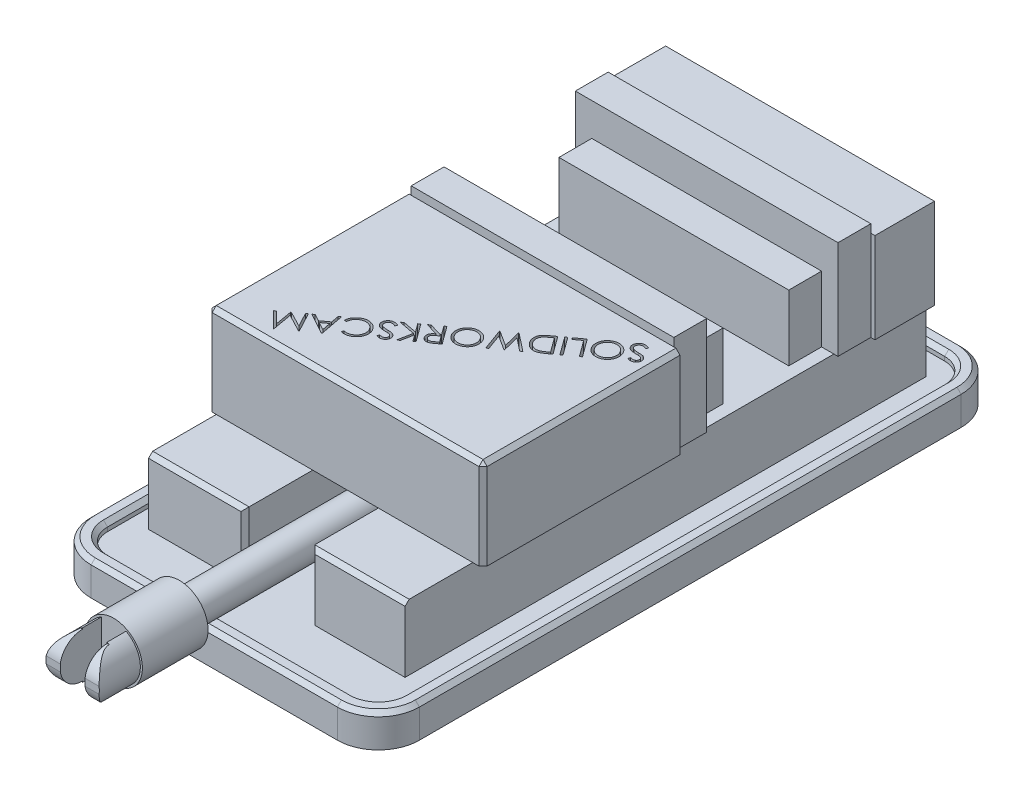
SolidWorks part; units mm, degrees
ref_plane "Plane1" through (0, 0, 0) normal (0, 0, 1) x (1, 0, 0)
ref_plane "Plane2" through (0, 0, 0) normal (0, 1, 0) x (1, 0, 0)
ref_plane "Plane3" through (0, 0, 0) normal (1, 0, 0) x (0, 0, -1)
sketch "Sketch1" plane through (0, 0, 0) normal (0, 0, 1) x (1, 0, 0)
  line L1 (-101.6, 0) -> (101.6, 0)
  line L2 (-101.6, 0) -> (-101.6, 76.2)
  line L3 (-101.6, 76.2) -> (101.6, 76.2)
  line L4 (101.6, 0) -> (101.6, 76.2)
extrude "Base-Extrude" add sketch "Sketch1" against normal blind 25.4
sketch "Sketch2" plane through (0, 0, 0) normal (0, 0, 1) x (1, 0, 0)
  line L0 (-101.6, 0) -> (101.6, 0) construction
  line L1 (-106.3625, 0) -> (106.3625, 0)
  line L2 (-106.3625, 0) -> (-106.3625, 69.85)
  line L3 (-106.3625, 69.85) -> (106.3625, 69.85)
  line L4 (106.3625, 0) -> (106.3625, 69.85)
  dimension "D1" = 69.85
extrude "Boss-Extrude1" add sketch "Sketch2" along normal blind 152.4
sketch "Sketch3" plane through (0, 0, 0) normal (0, -1, 0) x (1, 0, 0)
  line L1 (98.425, 204.7875) -> (25.4, 204.7875)
  line L2 (98.425, 204.7875) -> (98.425, -201.6125)
  line L3 (98.425, -201.6125) -> (25.4, -201.6125)
  line L4 (25.4, 204.7875) -> (25.4, -201.6125)
  line L5 (-100.0125, 204.7875) -> (-25.4, 204.7875)
  line L6 (-100.0125, 204.7875) -> (-100.0125, -201.6125)
  line L7 (-100.0125, -201.6125) -> (-25.4, -201.6125)
  line L8 (-25.4, 204.7875) -> (-25.4, -201.6125)
extrude "Boss-Extrude2" add sketch "Sketch3" along normal blind 50.8
sketch "Sketch4" plane through (0, 0, 0) normal (0, 1, 0) x (-1, 0, 0)
  line L1 (-104.775, -201.6125) -> (106.3625, -201.6125)
  line L2 (-104.775, -201.6125) -> (-104.775, -152.4)
  line L3 (-104.775, -152.4) -> (106.3625, -152.4)
  line L4 (106.3625, -201.6125) -> (106.3625, -152.4)
extrude "Boss-Extrude3" add sketch "Sketch4" along normal blind 69.85
sketch "Sketch5" plane through (0, 0, -152.4) normal (0, 0, 1) x (1, 0, 0)
  line L1 (-101.6, 0) -> (101.6, 0)
  line L2 (-101.6, 0) -> (-101.6, 76.2)
  line L3 (-101.6, 76.2) -> (101.6, 76.2)
  line L4 (101.6, 0) -> (101.6, 76.2)
extrude "Boss-Extrude4" add sketch "Sketch5" along normal blind 25.4
sketch "Sketch6" plane through (0, -50.8, 0) normal (0, -1, 0) x (1, 0, 0)
  line L1 (-95.25, 254) -> (95.25, 254)
  line L2 (-127, 222.25) -> (-127, -196.85)
  line L3 (-95.25, -228.6) -> (95.25, -228.6)
  line L4 (127, 222.25) -> (127, -196.85)
  arc A0 (127, 222.25) -> (95.25, 254) centre (95.25, 222.25) ccw
  arc A1 (-127, 222.25) -> (-95.25, 254) centre (-95.25, 222.25) cw
  arc A2 (-95.25, -228.6) -> (-127, -196.85) centre (-95.25, -196.85) cw
  arc A3 (127, -196.85) -> (95.25, -228.6) centre (95.25, -196.85) cw
  dimension "D1" = 31.75
extrude "Boss-Extrude5" add sketch "Sketch6" along normal blind 19.05
sketch "Sketch7" plane through (0, -69.85, 0) normal (0, -1, 0) x (1, 0, 0)
  line L1 (95.25, 254) -> (-95.25, 254)
  line L2 (127, 222.25) -> (127, -196.85)
  line L3 (95.25, -228.6) -> (-95.25, -228.6)
  line L4 (-127, 222.25) -> (-127, -196.85)
  line L5 (95.25, 241.3) -> (-95.25, 241.3)
  line L6 (114.3, 222.25) -> (114.3, -196.85)
  line L7 (95.25, -215.9) -> (-95.25, -215.9)
  line L8 (-114.3, 222.25) -> (-114.3, -196.85)
  arc A0 (-114.3, -196.85) -> (-95.25, -215.9) centre (-95.25, -196.85) ccw
  arc A1 (95.25, -215.9) -> (114.3, -196.85) centre (95.25, -196.85) ccw
  arc A2 (114.3, 222.25) -> (95.25, 241.3) centre (95.25, 222.25) ccw
  arc A3 (-114.3, 222.25) -> (-95.25, 241.3) centre (-95.25, 222.25) cw
  arc A4 (-127, 222.25) -> (-95.25, 254) centre (-95.25, 222.25) cw
  arc A5 (127, 222.25) -> (95.25, 254) centre (95.25, 222.25) ccw
  arc A6 (95.25, -228.6) -> (127, -196.85) centre (95.25, -196.85) ccw
  arc A7 (-127, -196.85) -> (-95.25, -228.6) centre (-95.25, -196.85) ccw
  point P22 (127, 254)
  point P27 (-127, -228.6)
extrude "Boss-Extrude6" add sketch "Sketch7" against normal blind 25.4
sketch "Sketch8" plane through (0, 0, -201.6125) normal (0, 0, -1) x (-1, 0, 0)
  line L0 (-25.4, 0) -> (25.4, 0) construction
  line L1 (-19.05, 0) -> (19.05, 0)
  line L2 (-19.05, 0) -> (-19.05, -19.0525)
  line L3 (-0.0025, -38.1) -> (0.0025, -38.1)
  line L4 (19.05, 0) -> (19.05, -19.0525)
  arc A0 (-0.0025, -38.1) -> (-19.05, -19.0525) centre (-0.0025, -19.0525) cw
  arc A1 (19.05, -19.0525) -> (0.0025, -38.1) centre (0.0025, -19.0525) cw
  dimension "D1" = 19.0475
extrude "Boss-Extrude7" add sketch "Sketch8" against normal blind 50.8
sketch "Sketch9" plane through (0, 0, -150.8125) normal (0, 0, 1) x (1, 0, 0)
  circle A0 centre (-0.0025, -19.0525) radius 12.6992
extrude "Boss-Extrude8" add sketch "Sketch9" along normal blind 482.6
sketch "Sketch10" plane through (0, 0, 331.7875) normal (0, 0, 1) x (1, 0, 0)
  circle A0 centre (-0.0025, -19.0525) radius 22.225
  dimension "D1" = 44.45
extrude "Boss-Extrude9" add sketch "Sketch10" against normal blind 50.8
sketch "Sketch12" plane through (0, 0, 331.7875) normal (0, 0, 1) x (1, 0, 0)
  line L0 (-9.5647, -0.7628) -> (-9.5647, -37.3372)
  line L1 (9.5596, -0.7601) -> (9.5596, -37.3399)
  arc A2 (-9.5647, -0.7628) -> (-9.5647, -37.3372) centre (0, -19.05) ccw
  arc A3 (9.5596, -37.3399) -> (9.5596, -0.7601) centre (0, -19.05) ccw
extrude "Boss-Extrude10" add sketch "Sketch12" along normal blind 31.75
sketch "Sketch13" plane through (0, 0, 0) normal (1, 0, 0) x (0, 0, -1)
  line L0 (-280.9875, -19.0525) -> (150.8125, -19.0525) construction
  line L1 (-346.3741, 4.5289) -> (-346.3741, -1.682)
  line L2 (-346.3741, -36.4231) -> (-346.3741, -44.7128)
  line L3 (-346.3741, 4.5289) -> (-380.0007, 4.5289)
  line L4 (-380.0007, 4.5289) -> (-380.0007, -44.7128)
  line L5 (-380.0007, -44.7128) -> (-346.3741, -44.7128)
  arc A0 (-346.3741, -1.682) -> (-346.3741, -36.4231) centre (-346.3741, -19.0525) ccw
extrude "Cut-Extrude3" cut sketch "Sketch13" against normal through all and the other way blind 31.75
sketch "Sketch14" plane through (9.5596, 0, 0) normal (-1, 0, 0) x (0, 0, 1)
  line L1 (280.9875, -19.0525) -> (-150.8125, -19.0525) construction
  line L3 (337.8589, -28.8337) -> (337.5634, -29.1906)
  line L4 (365.125, -34.925) -> (356.7289, -45.0631)
  line L5 (337.5634, -29.1906) -> (356.7289, -45.0631)
  line L7 (354.06, -9.2714) -> (354.7178, -8.4772)
  line L8 (365.125, -34.925) -> (373.8833, -24.3496)
  line L9 (354.7178, -8.4772) -> (373.8833, -24.3496)
  arc A0 (354.06, -9.2714) -> (337.8589, -28.8337) centre (345.9595, -19.0525) ccw
  dimension "D1" = 25.4
extrude "Boss-Extrude11" [suppressed] add sketch "Sketch14" along normal blind 19.05
sketch "Sketch15" [suppressed] plane through (0, -193.5743, 233.7351) normal (0, -0.6378, 0.7702) x (1, 0, 0)
  line L0 (0, 206.2589) -> (0, 196.955) construction
  circle A0 centre (0, 206.2589) radius 16.5133
extrude "Boss-Extrude12" [suppressed] add sketch "Sketch15" along normal blind 304.8 draft 1
sketch "Sketch17" [suppressed] plane through (0, -387.9874, 468.483) normal (0, -0.6378, 0.7702) x (1, 0, 0)
  line L0 (0, 206.2589) -> (0, 196.955) construction
  line L1 (0, 234.95) -> (0, 177.7858)
  line L2 (0, 239.7125) -> (0, 250.825) construction
  arc A0 (0, 177.7858) -> (0, 234.95) centre (0, 206.3679) ccw
revolve "Boss-Revolve1" [suppressed] add sketch "Sketch17" angle 360 about L2
sketch "Sketch19" plane through (0, 0, -127) normal (0, 0, 1) x (1, 0, 0)
  line L1 (-88.9, 0) -> (88.9, 0)
  line L2 (-88.9, 0) -> (-88.9, 50.8)
  line L3 (-88.9, 50.8) -> (88.9, 50.8)
  line L4 (88.9, 0) -> (88.9, 50.8)
extrude "Boss-Extrude14" add sketch "Sketch19" along normal blind 25.4
sketch "Sketch20" plane through (0, 0, -25.4) normal (0, 0, -1) x (-1, 0, 0)
  line L1 (-88.9, 0) -> (88.9, 0)
  line L2 (-88.9, 0) -> (-88.9, 50.8)
  line L3 (-88.9, 50.8) -> (88.9, 50.8)
  line L4 (88.9, 0) -> (88.9, 50.8)
extrude "Boss-Extrude15" add sketch "Sketch20" along normal blind 25.4
chamfer "Chamfer1" distance 3.175 angle 45 30 edges at (-127, -44.45, 12.7) (-117.7006, -44.45, -219.3006) (0, -44.45, -228.6) (117.7006, -44.45, -219.3006) (127, -44.45, 12.7) (117.7006, -44.45, 244.7006) (0, -44.45, 254) (-117.7006, -44.45, 244.7006) (-114.3, -44.45, 12.7) (-108.7204, -44.45, 235.7204) (0, -44.45, 241.3) (108.7204, -44.45, 235.7204) (114.3, -44.45, 12.7) (108.7204, -44.45, -210.3204) (0, -44.45, -215.9) (-108.7204, -44.45, -210.3204) (-106.3625, 69.85, 76.2) (0, 69.85, 152.4) (106.3625, 69.85, 76.2) (106.3625, 34.925, 152.4) (-106.3625, 34.925, 152.4) (-62.7063, 0, 204.7875) (-25.4, -25.4, 204.7875) (25.4, -25.4, 204.7875) (61.9125, 0, 204.7875) (-0.7937, 69.85, -201.6125) (98.425, -25.4, -201.6125) (-106.3625, 34.925, -201.6125) (-106.3625, 69.85, -177.0062) (104.775, 34.925, -201.6125)
sketch "Sketch21" plane through (0, 69.85, 0) normal (0, 1, 0) x (1, 0, 0)
  line L0 (101.6, 0) -> (-103.1875, -149.225)
sketch "Sketch22" plane through (0, 69.85, 0) normal (0, 1, 0) x (1, 0, 0)
  text T0 "  SOLIDWORKSCAM" font "Century Gothic" height in points 65
extrude "Cut-Extrude4" cut sketch "Sketch22" against normal blind 25.146
